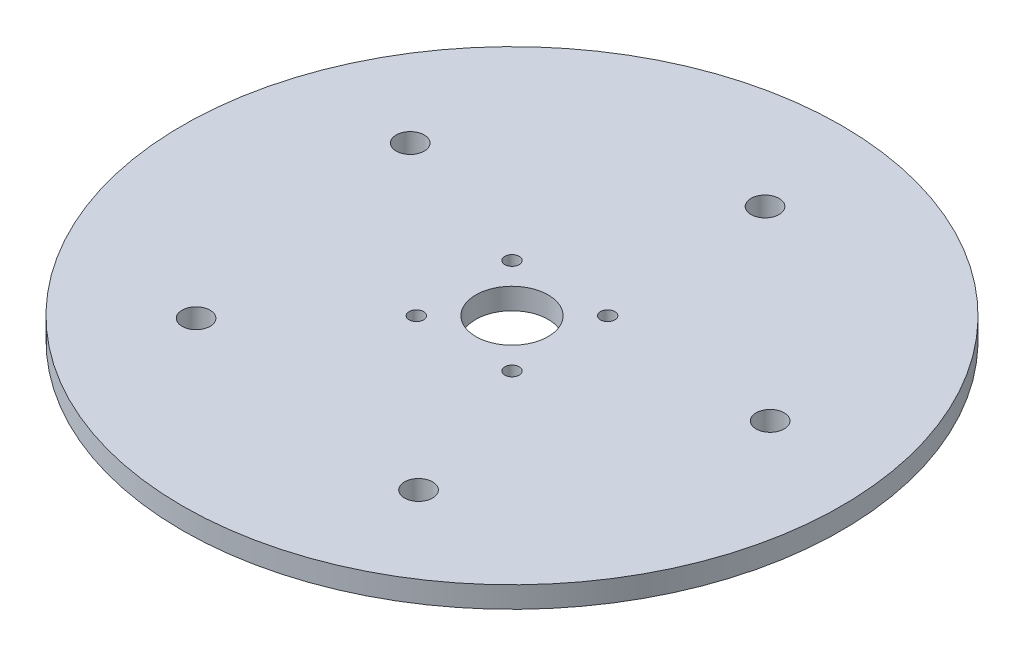
SolidWorks part; units mm, degrees
ref_plane "Front Plane" through (0, 0, 0) normal (0, 0, 1) x (1, 0, 0)
ref_plane "Top Plane" through (0, 0, 0) normal (0, 1, 0) x (1, 0, 0)
ref_plane "Right Plane" through (0, 0, 0) normal (1, 0, 0) x (0, 0, -1)
sketch "Sketch1" plane through (0, 0, 0) normal (0, 1, 0) x (1, 0, 0)
  circle A0 centre (0, 0) radius 77.5
  circle A1 centre (0, 0) radius 8.5
  dimension "D1" = 155
  dimension "D2" = 17
extrude "Body" add sketch "Sketch1" along normal blind 5
hole_wizard "M6 Clearance Hole1" positions "Sketch2" profile "Sketch3" hole size "M6" standard "ANSI Metric" end condition through all
sketch "Sketch2" plane through (0, 5, 0) normal (0, 1, 0) x (1, 0, 0)
  point P0 (7.5, 52)
  point P10 (51.7726, 8.936)
  point P11 (24.4972, -46.4773)
  point P12 (-36.6325, -37.6605)
  point P13 (-47.1373, 23.2018)
  point P15 (0, 0)
  dimension "D1" = 52
  dimension "D2" = 7.5
  dimension "D3" = 5
sketch "Sketch3" plane through (7.5, 5, -52) normal (1, 0, 0) x (0, 0, 1)
  line L0 (0, 0) -> (0, 5)
  line L1 (0, 5) -> (3.3, 5)
  line L2 (3.3, 5) -> (3.3, 0)
  line L5 (3.3, 0) -> (0, 0)
  line L11 (0, -6.35) -> (0, 107.95) construction
  dimension "Thru Hole Dia." = 6.6
  dimension "Thru Hole Depth" = 5
hole_wizard "M3 Clearance Hole1" positions "Sketch4" profile "Sketch5" hole size "M3" standard "ANSI Metric" end condition through all
sketch "Sketch4" plane through (0, 5, 0) normal (0, 1, 0) x (1, 0, 0)
  line L1 (11.25, -11.25) -> (-11.25, -11.25) construction
  line L2 (11.25, -11.25) -> (11.25, 11.25) construction
  line L3 (11.25, 11.25) -> (-11.25, 11.25) construction
  line L4 (-11.25, -11.25) -> (-11.25, 11.25) construction
  line L5 (11.25, -11.25) -> (-11.25, 11.25) construction
  line L6 (11.25, 11.25) -> (-11.25, -11.25) construction
  point P1 (0, 0)
  point P2 (-11.25, 11.25)
  point P21 (11.25, -11.25)
  point P22 (11.25, 11.25)
  point P23 (-11.25, -11.25)
  dimension "D1" = 22.5
sketch "Sketch5" plane through (0, 5, 0) normal (1, 0, 0) x (0, 0, 1)
  line L0 (0, 0) -> (0, 5)
  line L1 (0, 5) -> (1.7, 5)
  line L2 (1.7, 5) -> (1.7, 0)
  line L5 (1.7, 0) -> (0, 0)
  line L11 (0, -6.35) -> (0, 107.95) construction
  dimension "Thru Hole Dia." = 3.4
  dimension "Thru Hole Depth" = 5
